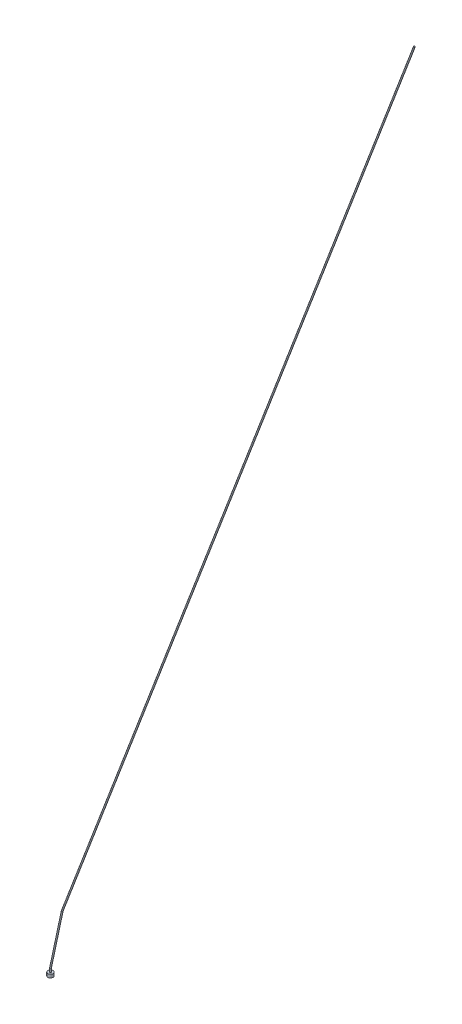
SolidWorks part; units mm, degrees
ref_plane "Front Plane" through (0, 0, 0) normal (0, 0, 1) x (1, 0, 0)
ref_plane "Top Plane" through (0, 0, 0) normal (0, 1, 0) x (1, 0, 0)
ref_plane "Right Plane" through (0, 0, 0) normal (1, 0, 0) x (0, 0, -1)
sketch "Sketch1" plane through (0, 0, 0) normal (0, 0, 1) x (1, 0, 0)
  line L0 (55, -42.5) -> (73, 42.5)
  line L1 (-73, 42.5) -> (73, 42.5) construction
  line L2 (-73, 42.5) -> (-73, -42.5) construction
  line L3 (-73, -42.5) -> (73, -42.5) construction
  line L4 (73, 42.5) -> (73, -42.5) construction
  line L5 (-73, 42.5) -> (73, -42.5) construction
  line L6 (-73, -42.5) -> (73, 42.5) construction
  line L7 (73, 42.5) -> (611.965, 1457.5)
  line L8 (55, -42.5) -> (55, -52.5)
  point P0 (0, 0)
  point P9 (55, -42.5)
  point P11 (611.965, 1457.5)
  dimension "D1" = 85
  dimension "D2" = 146
  dimension "D3" = 611.965
  dimension "D4" = 1500
  dimension "D5" = 55
  dimension "D6" = 10
sweep "Sweep1" add path "Sketch1" circular profile diameter 2 parameters "D3"=2
sketch "Sketch10" plane through (0, -52.5, 0) normal (0, -1, 0) x (1, 0, 0)
  circle A0 centre (55, 0) radius 4
  dimension "D1" = 8
extrude "Boss-Extrude1" add sketch "Sketch10" against normal blind 5
